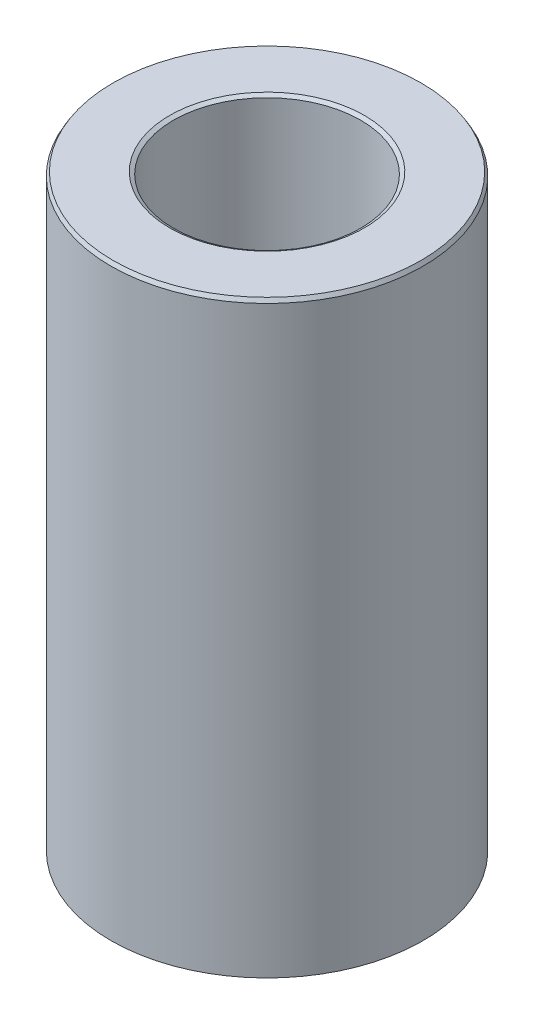
SolidWorks part; units mm, degrees
ref_plane "Front Plane" through (0, 0, 0) normal (0, 0, 1) x (1, 0, 0)
ref_plane "Top Plane" through (0, 0, 0) normal (0, 1, 0) x (1, 0, 0)
ref_plane "Right Plane" through (0, 0, 0) normal (1, 0, 0) x (0, 0, -1)
sketch "Sketch1" plane through (0, 0, 0) normal (0, 1, 0) x (1, 0, 0)
  circle A0 centre (0, 0) radius 47.5
  dimension "SLEEVE_OD" = 95
extrude "Boss-Extrude1" add sketch "Sketch1" along normal blind 179.574
sketch "Sketch2" plane through (0, 0, 0) normal (0, 1, 0) x (1, 0, 0)
  circle A0 centre (0, 0) radius 28.49
  dimension "BORE_D" = 56.98
extrude "Cut-Extrude1" cut sketch "Sketch2" along normal through all
chamfer "Chamfer1" distance 1.1574 angle 30 4 edges at (0, 179.574, 28.49) (0, 0, 28.49) (0, 0, 47.5) (0, 179.574, 47.5) first distance on face at (0, 179.574, 28.49) first distance on face at (0, 0, 28.49) first distance on face at (0, 179.574, 47.5)
